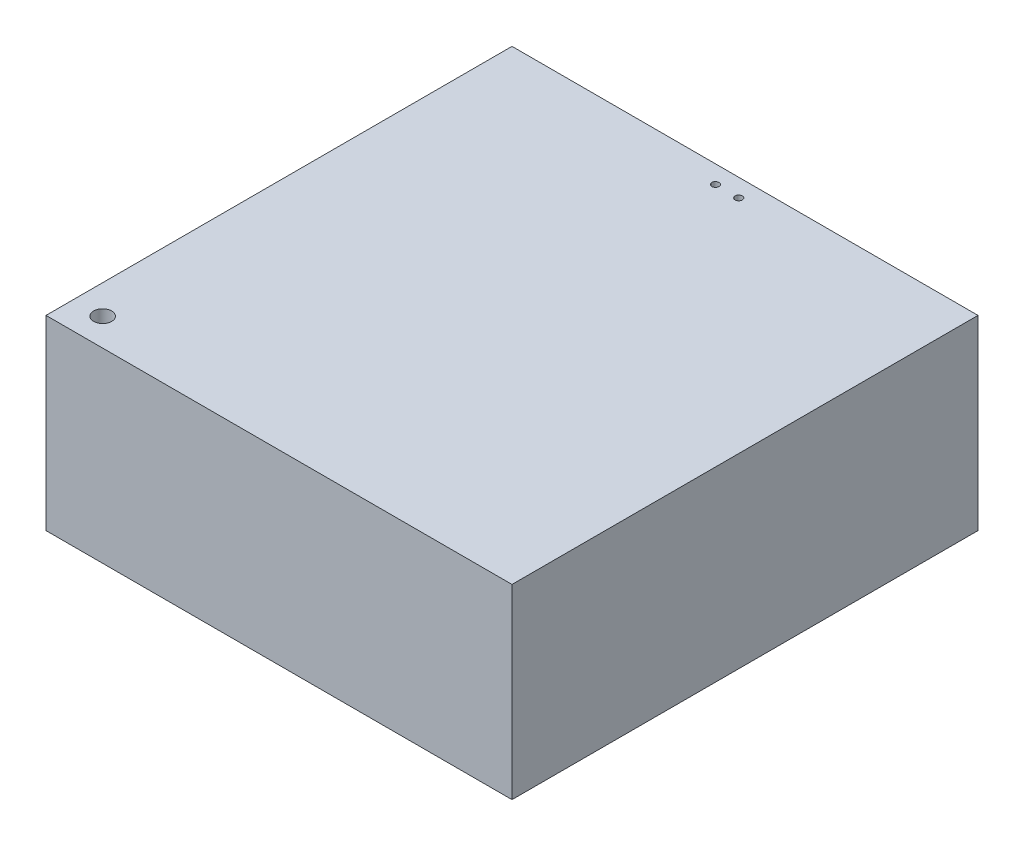
SolidWorks part; units mm, degrees
ref_plane "Front Plane" through (0, 0, 0) normal (0, 0, 1) x (1, 0, 0)
ref_plane "Top Plane" through (0, 0, 0) normal (0, 1, 0) x (1, 0, 0)
ref_plane "Right Plane" through (0, 0, 0) normal (1, 0, 0) x (0, 0, -1)
sketch "Sketch1" plane through (0, 0, 0) normal (0, 1, 0) x (1, 0, 0)
  line L1 (-65, 65) -> (65, 65)
  line L2 (-65, 65) -> (-65, -65)
  line L3 (-65, -65) -> (65, -65)
  line L4 (65, 65) -> (65, -65)
  line L5 (-65, 65) -> (65, -65) construction
  line L6 (-65, -65) -> (65, 65) construction
  point P0 (0, 0)
  dimension "D1" = 130
  dimension "D2" = 130
extrude "Boss-Extrude1" add sketch "Sketch1" along normal blind 52
sketch "Sketch2" plane through (0, 52, 0) normal (0, 1, 0) x (1, 0, 0)
  circle A0 centre (-56.9079, -57.2901) radius 2.5272
extrude "Cut-Extrude1" cut sketch "Sketch2" against normal blind 10
sketch "Sketch3" plane through (65, 0, 0) normal (1, 0, 0) x (0, 0, -1)
  circle A0 centre (65, 52) radius 9
  dimension "D1" = 18
extrude "Boss-Extrude2" [suppressed] add sketch "Sketch3" against normal up to surface (130 mm away) up to face at (-65, 26, 0)
sketch "Sketch4" [suppressed] plane through (65, 0, 0) normal (1, 0, 0) x (0, 0, -1)
  circle A0 centre (65, 52) radius 7.1
  dimension "D1" = 14.2
extrude "Cut-Extrude2" [suppressed] cut sketch "Sketch4" against normal up to surface (130 mm away) up to face at (-65, 26, 0)
sketch "Sketch5" plane through (0, 52, 0) normal (0, 1, 0) x (1, 0, 0)
  line L0 (0, 0) -> (0, 69.932) construction
  line L1 (65, 65) -> (-65, 65) construction
  circle A0 centre (-3.25, 60) radius 1
  circle A1 centre (3.25, 60) radius 1
  point P5 (0, 0)
  dimension "D2" = 2
  dimension "D1" = 6.5
  dimension "D3" = 5
extrude "Cut-Extrude3" cut sketch "Sketch5" against normal blind 5
